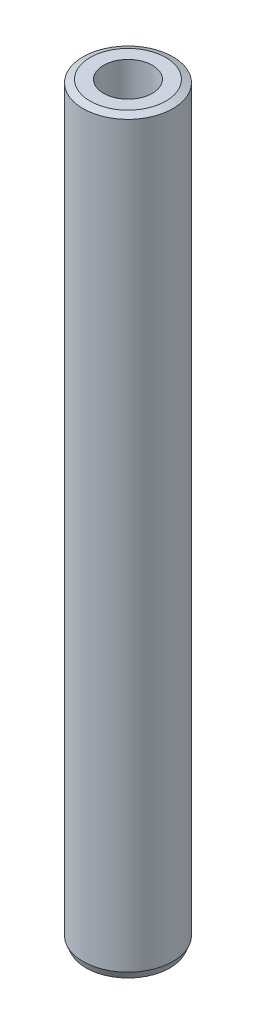
SolidWorks part; units mm, degrees
ref_plane "Front Plane" through (0, 0, 0) normal (0, 0, 1) x (1, 0, 0)
ref_plane "Top Plane" through (0, 0, 0) normal (0, 1, 0) x (1, 0, 0)
ref_plane "Right Plane" through (0, 0, 0) normal (1, 0, 0) x (0, 0, -1)
sketch "Sketch1" plane through (0, 0, 0) normal (0, 1, 0) x (1, 0, 0)
  circle A0 centre (0, 0) radius 32.5
  dimension "SHAFT_OD" = 65
extrude "Boss-Extrude1" add sketch "Sketch1" along normal blind 541.5409
sketch "Sketch2" plane through (0, 0, 0) normal (0, 1, 0) x (1, 0, 0)
  circle A0 centre (0, 0) radius 17.6354
  dimension "BORE_D" = 35.2709
extrude "Cut-Extrude1" cut sketch "Sketch2" along normal through all
chamfer "Chamfer1" distance 2.1154 angle 67.582 2 edges at (0, 541.5409, 32.5) (0, 0, 32.5) first distance on face at (0, 541.5409, 32.5) first distance on face at (0, 0, 17.6354)
